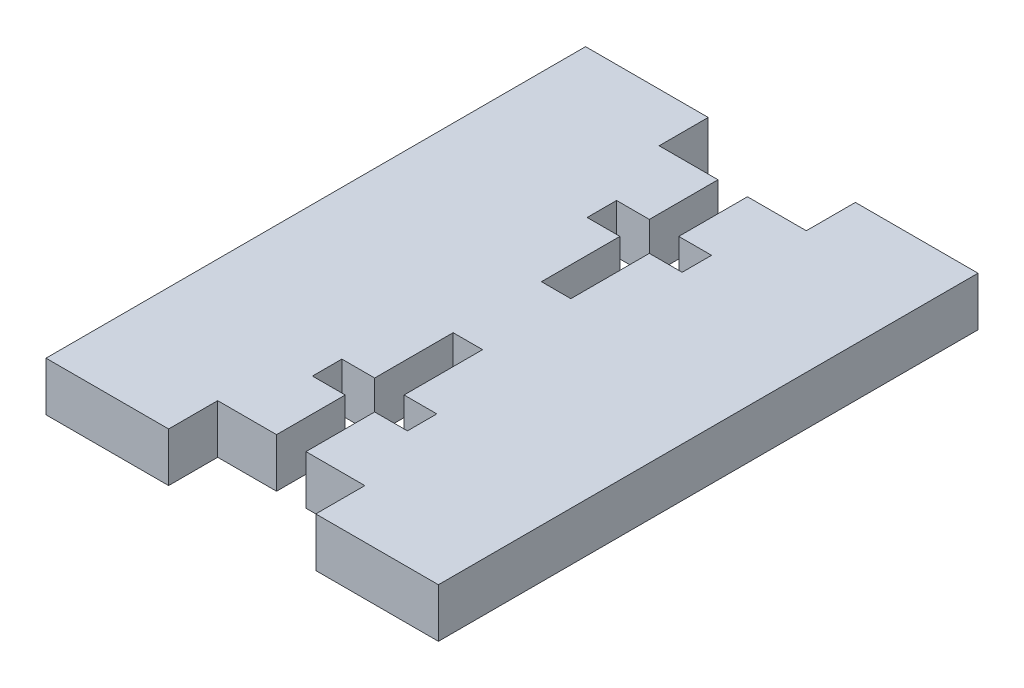
SolidWorks part; units mm, degrees
material "PVC rigido"
ref_plane "Piano frontale" through (0, 0, 0) normal (0, 0, 1) x (1, 0, 0)
ref_plane "Piano superiore" through (0, 0, 0) normal (0, 1, 0) x (1, 0, 0)
ref_plane "Piano destro" through (0, 0, 0) normal (1, 0, 0) x (0, 0, -1)
sketch "Schizzo1" plane through (0, 0, 0) normal (0, 1, 0) x (1, 0, 0)
  line L1 (-54.5649, -28.2811) -> (-14.5649, -28.2811)
  line L2 (-54.5649, -28.2811) -> (-54.5649, 26.7189)
  line L3 (-54.5649, 26.7189) -> (-14.5649, 26.7189)
  line L4 (-14.5649, -28.2811) -> (-14.5649, 26.7189)
  dimension "D1" = 40
  dimension "D2" = 55
sketch "Schizzo2" plane through (0, 0, 0) normal (0, 1, 0) x (1, 0, 0)
  line L0 (-54.5649, -0.7811) -> (-14.5649, -0.7811) construction
  line L5 (-54.5649, -28.2811) -> (-54.5649, 26.7189) construction
  line L6 (-14.5649, -28.2811) -> (-14.5649, 26.7189) construction
  line L7 (-34.5649, -28.2811) -> (-34.5649, 26.7189) construction
  line L8 (-54.5649, -28.2811) -> (-14.5649, -28.2811) construction
  line L9 (-54.5649, 26.7189) -> (-14.5649, 26.7189) construction
  line L22 (-42.0649, -28.2811) -> (-27.0649, -28.2811)
  line L23 (-42.0649, -28.2811) -> (-42.0649, -23.2811)
  line L24 (-42.0649, -23.2811) -> (-27.0649, -23.2811)
  line L25 (-27.0649, -28.2811) -> (-27.0649, -23.2811)
  line L26 (-42.0649, 26.7189) -> (-42.0649, 21.7189)
  line L27 (-42.0649, 21.7189) -> (-27.0649, 21.7189)
  line L28 (-27.0649, 26.7189) -> (-27.0649, 21.7189)
  line L29 (-42.0649, 26.7189) -> (-27.0649, 26.7189)
  point P33 (-34.5649, -23.2811)
  dimension "D3" = 15
  dimension "D4" = 5
extrude "Estrusione-Estrusione2" add sketch "Schizzo1" against normal blind 5
extrude "Taglio-Estrusione1" cut sketch "Schizzo2" against normal through all
sketch "Schizzo3" plane through (0, 0, 0) normal (0, 1, 0) x (1, 0, 0)
  line L1 (-36.0649, -23.2811) -> (-33.0649, -23.2811)
  line L2 (-54.5649, -0.7811) -> (-14.5649, -0.7811) construction
  line L3 (-54.5649, 26.7189) -> (-54.5649, -28.2811) construction
  line L15 (-14.5649, -28.2811) -> (-14.5649, 26.7189) construction
  line L19 (-34.5649, 21.7189) -> (-34.5649, -23.2811) construction
  line L20 (-42.0649, 21.7189) -> (-27.0649, 21.7189) construction
  line L21 (-27.0649, -23.2811) -> (-42.0649, -23.2811) construction
  line L26 (-36.0649, -23.2811) -> (-36.0649, -16.2811)
  line L27 (-36.0649, -16.2811) -> (-39.4049, -16.2811)
  line L28 (-39.4049, -16.2811) -> (-39.4049, -13.2811)
  line L29 (-39.4049, -13.2811) -> (-36.0649, -13.2811)
  line L30 (-36.0649, -13.2811) -> (-36.0649, -5.2811)
  line L31 (-36.0649, -5.2811) -> (-33.0649, -5.2811)
  line L32 (-33.0649, -5.2811) -> (-33.0649, -13.2811)
  line L33 (-33.0649, -13.2811) -> (-29.7249, -13.2811)
  line L34 (-29.7249, -13.2811) -> (-29.7249, -16.2811)
  line L35 (-29.7249, -16.2811) -> (-33.0649, -16.2811)
  line L36 (-33.0649, -16.2811) -> (-33.0649, -23.2811)
  line L60 (-36.0649, 3.7189) -> (-33.0649, 3.7189)
  line L61 (-36.0649, 11.7189) -> (-36.0649, 3.7189)
  line L62 (-39.4049, 11.7189) -> (-36.0649, 11.7189)
  line L63 (-39.4049, 14.7189) -> (-39.4049, 11.7189)
  line L64 (-36.0649, 14.7189) -> (-39.4049, 14.7189)
  line L65 (-36.0649, 21.7189) -> (-36.0649, 14.7189)
  line L66 (-36.0649, 21.7189) -> (-33.0649, 21.7189)
  line L67 (-33.0649, 14.7189) -> (-33.0649, 21.7189)
  line L68 (-29.7249, 14.7189) -> (-33.0649, 14.7189)
  line L69 (-29.7249, 11.7189) -> (-29.7249, 14.7189)
  line L70 (-33.0649, 11.7189) -> (-29.7249, 11.7189)
  line L71 (-33.0649, 3.7189) -> (-33.0649, 11.7189)
  point P53 (-34.5649, -23.2811)
  dimension "D8" = 3
  dimension "D9" = 7
  dimension "D10" = 8
  dimension "D11" = 3
  dimension "D12" = 3.34
extrude "Taglio-Estrusione3" cut sketch "Schizzo3" against normal through all
